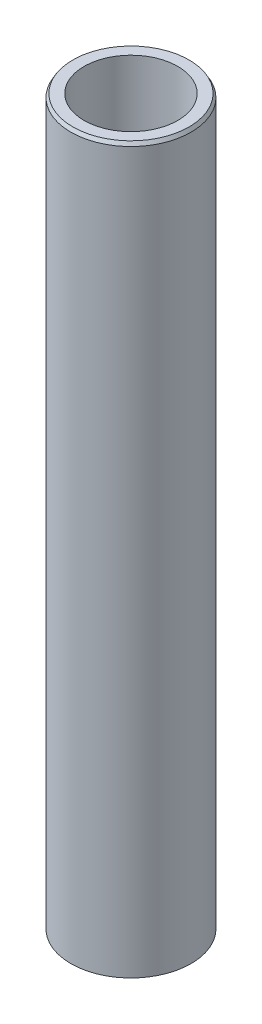
SolidWorks part; units mm, degrees
ref_plane "Front Plane" through (0, 0, 0) normal (0, 0, 1) x (1, 0, 0)
ref_plane "Top Plane" through (0, 0, 0) normal (0, 1, 0) x (1, 0, 0)
ref_plane "Right Plane" through (0, 0, 0) normal (1, 0, 0) x (0, 0, -1)
sketch "Sketch1" plane through (0, 0, 0) normal (0, 1, 0) x (1, 0, 0)
  circle A0 centre (0, 0) radius 45
  dimension "SHAFT_OD" = 90
extrude "Boss-Extrude1" add sketch "Sketch1" along normal blind 543.1389
sketch "Sketch2" plane through (0, 0, 0) normal (0, 1, 0) x (1, 0, 0)
  circle A0 centre (0, 0) radius 35.0775
  dimension "BORE_D" = 70.1549
extrude "Cut-Extrude1" cut sketch "Sketch2" along normal through all
chamfer "Chamfer1" distance 2.6348 angle 30 2 edges at (0, 543.1389, 45) (0, 0, 45) first distance on face at (0, 543.1389, 45) first distance on face at (0, 0, 35.0775)
